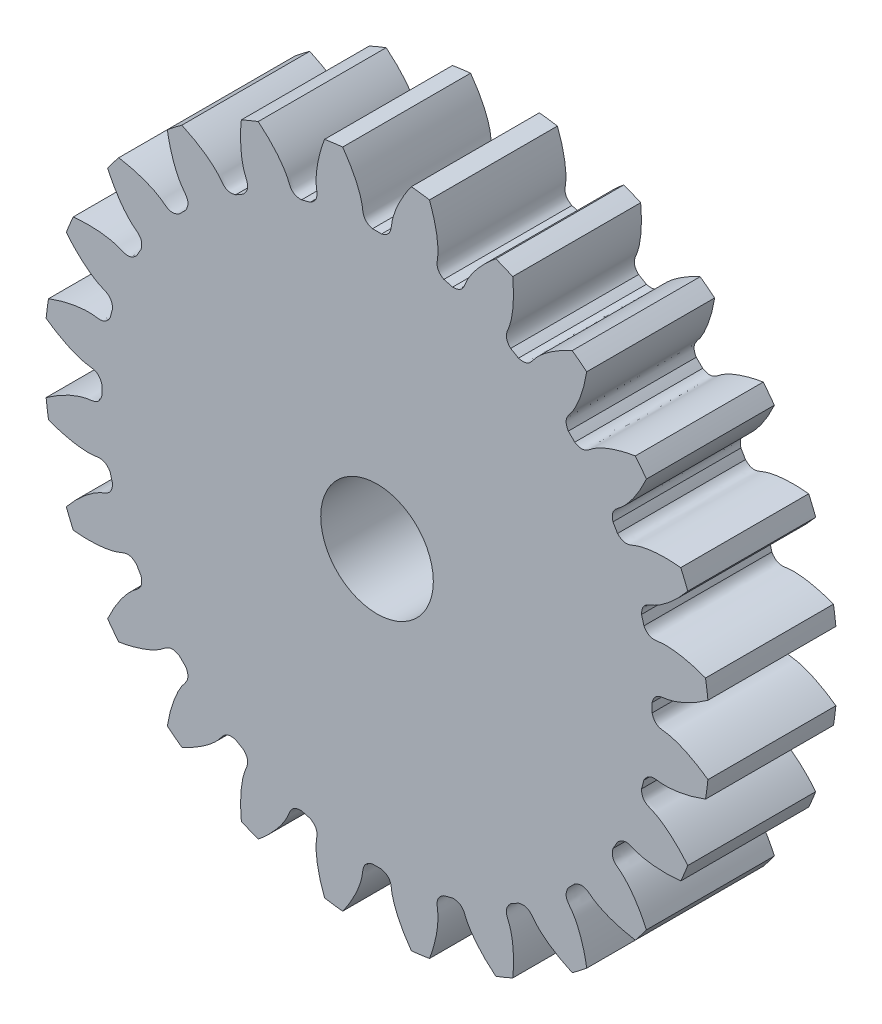
SolidWorks part; units mm, degrees
ref_plane "前视基准面" through (0, 0, 0) normal (0, 0, 1) x (1, 0, 0)
ref_plane "上视基准面" through (0, 0, 0) normal (0, 1, 0) x (1, 0, 0)
ref_plane "右视基准面" through (0, 0, 0) normal (1, 0, 0) x (0, 0, -1)
sketch "草图1" plane through (0, 0, 0) normal (0, 0, 1) x (1, 0, 0)
  circle A0 centre (0, 0) radius 6.5
extrude "凸台-拉伸1" add sketch "草图1" along normal blind 2.5
ref_axis "基准轴1" through (0, 0, 2.5) along (0, 0, -1)
sketch "草图2" plane through (0, 0, 0) normal (0, 0, 1) x (1, 0, 0)
  line L0 (0, 0) -> (0, 6.5) construction
  circle A0 centre (0, 0) radius 6.5 construction
  arc A1 (0.0884, 5.3743) -> (-0.0884, 5.3743) centre (0, 0) ccw
  arc A2 (1.5578, 7.3471) -> (-1.5578, 7.3471) centre (0, 0) ccw
  spline S0 degree 3 poles (0.0884, 5.3743) (0.284, 5.4284) (0.2695, 5.5579) (0.2931, 5.6863) (0.2965, 5.7029) (0.3007, 5.7216) (0.3058, 5.7424) (0.312, 5.7653) (0.3191, 5.7902) (0.3275, 5.8171) (0.3371, 5.846) (0.348, 5.8769) (0.3604, 5.9096) (0.3742, 5.9441) (0.3896, 5.9805) (0.4067, 6.0185) (0.4254, 6.0583) (0.446, 6.0997) (0.4684, 6.1427) (0.4928, 6.1872) (0.5192, 6.2332) (0.5476, 6.2806) (0.5782, 6.3293) (0.611, 6.3792) (0.6461, 6.4304) (0.6834, 6.4827) (0.7232, 6.536) (0.7654, 6.5903) (0.8101, 6.6456) (0.8574, 6.7016) (0.9073, 6.7583) (0.9598, 6.8158) (1.015, 6.8738) (1.0729, 6.9322) (1.1336, 6.9911) (1.1972, 7.0503) (1.2635, 7.1097) (1.3328, 7.1693) (1.4302, 7.2497) (1.506, 7.3084) (1.5578, 7.3471) knots 0 0 0 0 0.143961 0.149818 0.156577 0.164236 0.172796 0.182258 0.19262 0.203884 0.216049 0.229115 0.243082 0.25795 0.273719 0.290389 0.30796 0.326433 0.345806 0.366081 0.387257 0.409333 0.432311 0.45619 0.48097 0.506651 0.533234 0.560717 0.589101 0.618387 0.648574 0.679661 0.71165 0.74454 0.778331 0.813023 0.848616 0.885111 0.922506 1 1 1 1
  spline S1 degree 3 poles (-0.0884, 5.3743) (-0.284, 5.4284) (-0.2695, 5.5579) (-0.2931, 5.6863) (-0.2965, 5.7029) (-0.3007, 5.7216) (-0.3058, 5.7424) (-0.312, 5.7653) (-0.3191, 5.7902) (-0.3275, 5.8171) (-0.3371, 5.846) (-0.348, 5.8769) (-0.3604, 5.9096) (-0.3742, 5.9441) (-0.3896, 5.9805) (-0.4067, 6.0185) (-0.4254, 6.0583) (-0.446, 6.0997) (-0.4684, 6.1427) (-0.4928, 6.1872) (-0.5192, 6.2332) (-0.5476, 6.2806) (-0.5782, 6.3293) (-0.611, 6.3792) (-0.6461, 6.4304) (-0.6834, 6.4827) (-0.7232, 6.536) (-0.7654, 6.5903) (-0.8101, 6.6456) (-0.8574, 6.7016) (-0.9073, 6.7583) (-0.9598, 6.8158) (-1.015, 6.8738) (-1.0729, 6.9322) (-1.1336, 6.9911) (-1.1972, 7.0503) (-1.2635, 7.1097) (-1.3328, 7.1693) (-1.4302, 7.2497) (-1.506, 7.3084) (-1.5578, 7.3471) knots 0 0 0 0 0.143961 0.149818 0.156577 0.164236 0.172796 0.182258 0.19262 0.203884 0.216049 0.229115 0.243082 0.25795 0.273719 0.290389 0.30796 0.326433 0.345806 0.366081 0.387257 0.409333 0.432311 0.45619 0.48097 0.506651 0.533234 0.560717 0.589101 0.618387 0.648574 0.679661 0.71165 0.74454 0.778331 0.813023 0.848616 0.885111 0.922506 1 1 1 1
extrude "切除-拉伸1" cut sketch "草图2" along normal through all
pattern_circular "阵列(圆周)1" count 24 every 15 about axis through (0, 0, 2.5) along (0, 0, -1) of "切除-拉伸1"
sketch "草图3" plane through (0, 0, 0) normal (0, 0, 1) x (1, 0, 0)
  circle A0 centre (0, 0) radius 6 construction
  dimension "Dn" = 12
sketch "草图4" plane through (0, 0, 0) normal (0, 0, -1) x (-1, 0, 0)
  circle A0 centre (0, 0) radius 1.1
  dimension "D1" = 2.2
extrude "切除-拉伸2" cut sketch "草图4" against normal up to next
